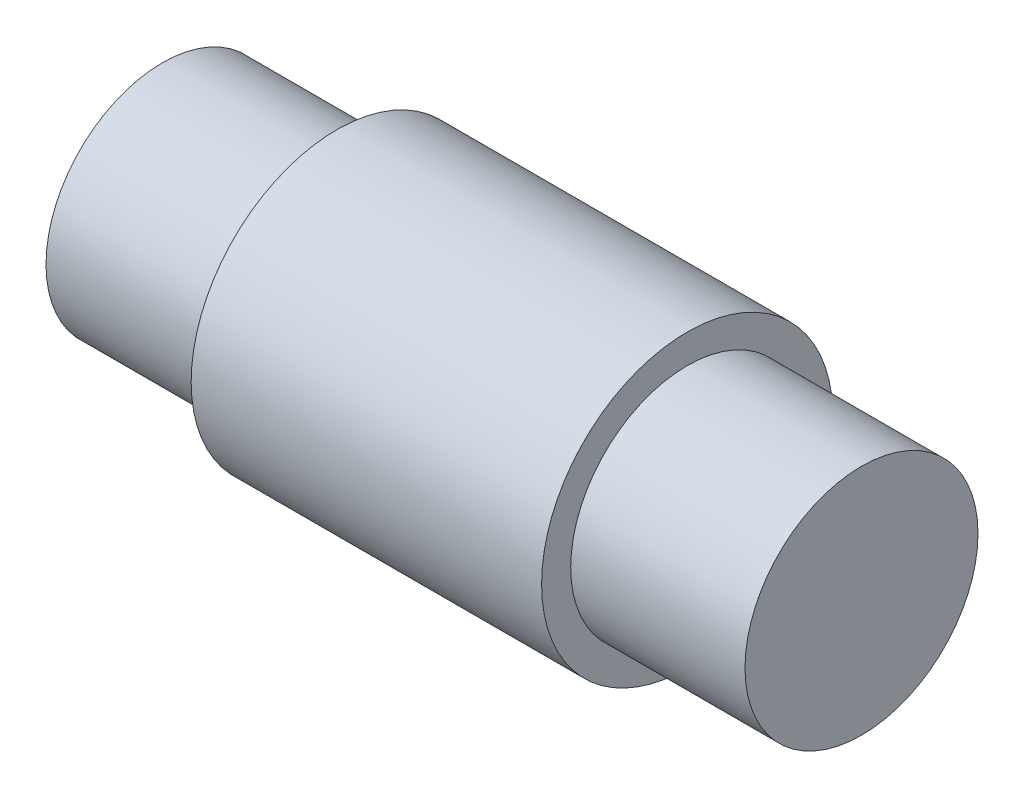
SolidWorks part; units mm, degrees
material "Alloy Steel"
ref_plane "Front Plane" through (0, 0, 0) normal (0, 0, 1) x (1, 0, 0)
ref_plane "Top Plane" through (0, 0, 0) normal (0, 1, 0) x (1, 0, 0)
ref_plane "Right Plane" through (0, 0, 0) normal (1, 0, 0) x (0, 0, -1)
sketch "Sketch1" plane through (0, 0, 0) normal (0, 0, 1) x (1, 0, 0)
  line L0 (-76.4565, 0) -> (100.0218, 0) construction
  line L1 (-9.525, 0) -> (-9.525, 3.175)
  line L2 (-9.525, 3.175) -> (-4.775, 3.175)
  line L3 (-4.775, 3.175) -> (-4.775, 3.9688)
  line L4 (-4.775, 3.9688) -> (4.775, 3.9688)
  line L5 (4.775, 3.9688) -> (4.775, 3.175)
  line L6 (4.775, 3.175) -> (9.525, 3.175)
  line L7 (9.525, 3.175) -> (9.525, 0)
  line L8 (9.525, 0) -> (-9.525, 0)
  dimension "D1" = 4.75
  dimension "D2" = 19.05
  dimension "D3" = 7.9375
  dimension "D4" = 6.35
revolve "Revolve1" add sketch "Sketch1" angle 360 about L0
